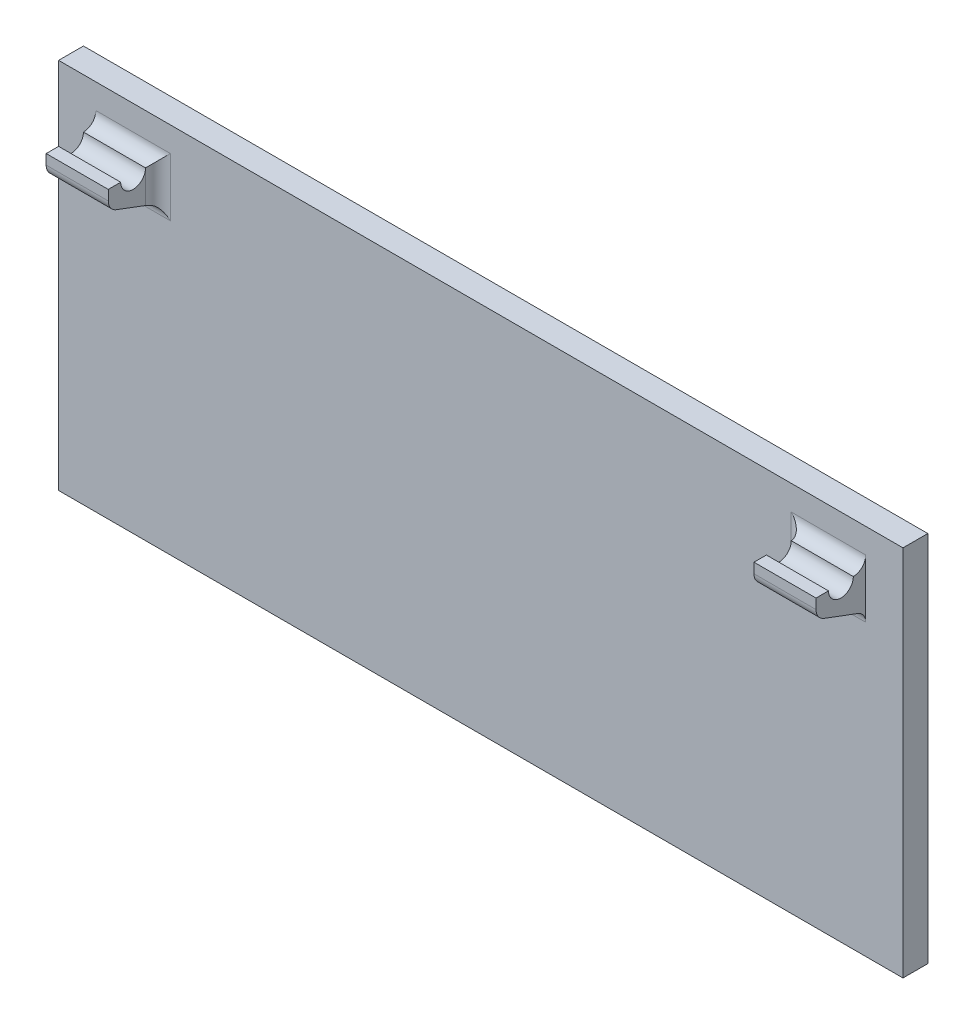
SolidWorks part; units mm, degrees
material "AISI 4340 Steel, annealed"
ref_plane "Front Plane" through (0, 0, 0) normal (0, 0, 1) x (1, 0, 0)
ref_plane "Top Plane" through (0, 0, 0) normal (0, 1, 0) x (1, 0, 0)
ref_plane "Right Plane" through (0, 0, 0) normal (1, 0, 0) x (0, 0, -1)
sketch "Sketch1" plane through (0, 0, 0) normal (0, 0, 1) x (1, 0, 0)
  line L1 (-170, 75) -> (170, 75)
  line L2 (-170, 75) -> (-170, -75)
  line L3 (-170, -75) -> (170, -75)
  line L4 (170, 75) -> (170, -75)
  line L5 (-170, 75) -> (170, -75) construction
  line L6 (-170, -75) -> (170, 75) construction
  point P0 (0, 0)
  dimension "D1" = 340
  dimension "D2" = 150
extrude "Vertical portion" add sketch "Sketch1" along normal blind 10
ref_plane "Plane1" through (155, 0, 0) normal (1, 0, 0) x (0, 0, -1)
sketch "Sketch4" plane through (155, 0, 0) normal (1, 0, 0) x (0, 0, -1)
  line L0 (-10, 75) -> (0, 75) construction
  line L1 (-10, 45) -> (-30, 52.5)
  line L2 (-15, 60) -> (-10, 60)
  line L3 (-10, -75) -> (-10, 75) construction
  line L4 (-10, 60) -> (-10, 55)
  line L5 (-10, 55) -> (-10, 45)
  line L6 (-10, 45) -> (-30, 45) construction
  line L7 (-30, 52.5) -> (-30, 60)
  line L8 (-30, 60) -> (-25, 60)
  line L9 (-30, 52.5) -> (-30, 45) construction
  line L10 (-10, -75) -> (-10, 75) construction
  arc A0 (-25, 60) -> (-15, 60) centre (-20, 60) ccw
  dimension "D1" = 10
  dimension "D6" = 15
  dimension "D2" = 10
  dimension "D3" = 10
  dimension "D4" = 5
  dimension "D5" = 20
extrude "Shaft adapter right" add sketch "Sketch4" against normal blind 25 contours L7 L8 A0 L2 L4 L5 L1
mirror "Shaft adapter left" about plane through (0, 0, 0) normal (1, 0, 0) of "Shaft adapter right"
fillet "Shaft adapter fillets" radius 5 8 edges at (-142.5, 52.5, 30) (142.5, 52.5, 30) (130, 52.5, 10) (-130, 52.5, 10) (-142.5, 45, 10) (142.5, 45, 10) (142.5, 60, 10) (-142.5, 60, 10)
